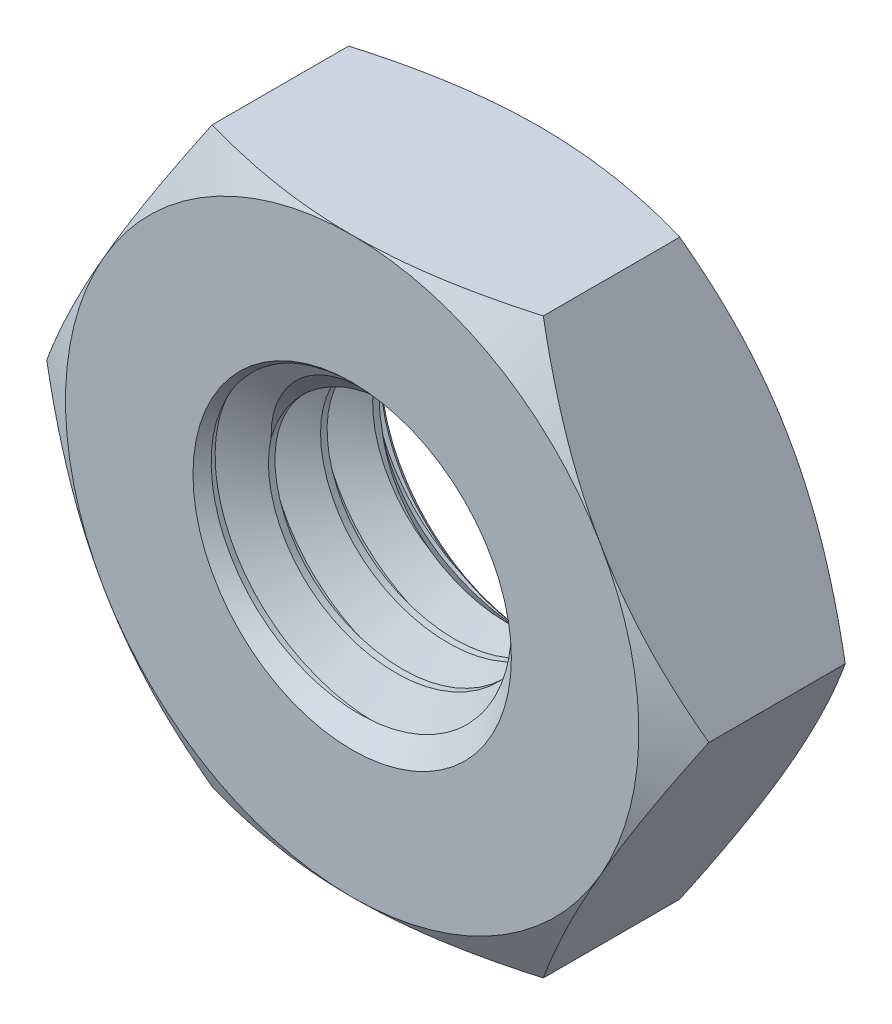
SolidWorks part; units mm, degrees
ref_plane "Front Plane" through (0, 0, 0) normal (0, 0, 1) x (1, 0, 0)
ref_plane "Top Plane" through (0, 0, 0) normal (0, 1, 0) x (1, 0, 0)
ref_plane "Right Plane" through (0, 0, 0) normal (1, 0, 0) x (0, 0, -1)
sketch "Sketch1" plane through (0, 0, 0) normal (1, 0, 0) x (0, 0, -1)
  line L0 (0, 2.75) -> (0, -2.75) construction
  line L1 (-0.9, 0) -> (0.9, 0) construction
  line L2 (-0.9, 1.5) -> (-0.9, -1.5) construction
  line L3 (-0.9, 1.5) -> (-0.4, 1.5) construction
  line L4 (-1.3687, 1.5541) -> (-0.8687, 1.5541) construction
  line L5 (-0.8687, 1.5541) -> (-0.9, 1.5) construction
  line L6 (-0.9, 1.5) -> (-1.1187, 1.1211) construction
  line L7 (-1.1187, 1.1211) -> (-1.3375, 1.5) construction
  line L8 (-1.3375, 1.5) -> (-1.3687, 1.5541) construction
  line L9 (-1.3375, 1.5) -> (-0.9, 1.5) construction
  line L10 (-1.15, 1.1752) -> (-1.0875, 1.1752) construction
  line L11 (-1.1187, 1.1752) -> (-1.1187, 1.1211) construction
  line L12 (-1.1187, 1.5541) -> (-1.1187, 1.5) construction
  point P4 (0, 0)
  point P8 (0, 0)
  point P11 (-0.9, 0)
  dimension "Thread OD" = 3
  dimension "Width" = 5.5
  dimension "Height" = 1.8
  dimension "D1" = 60
  dimension "D2" = 0.0625
  dimension "Thread Pitch" = 0.5
sketch "Sketch2" plane through (0, 0, 0) normal (0, 0, 1) x (1, 0, 0)
  line L1 (-1.5877, 2.75) -> (-3.1754, 0)
  line L2 (-3.1754, 0) -> (-1.5877, -2.75)
  line L3 (-1.5877, -2.75) -> (1.5877, -2.75)
  line L4 (1.5877, -2.75) -> (3.1754, 0)
  line L5 (3.1754, 0) -> (1.5877, 2.75)
  line L6 (1.5877, 2.75) -> (-1.5877, 2.75)
  circle A0 centre (0, 0) radius 2.75 construction
  circle A1 centre (0, 0) radius 1.5
extrude "Boss-Extrude1" add sketch "Sketch2" along normal up to vertex (0.9 mm away) and the other way up to vertex (0.9 mm away) up to point (0, 0, 0.9) other way up to point (0, 0, -0.9)
sketch "Sketch3" plane through (0, 0, 0.9) normal (0, 0, 1) x (1, 0, 0)
  circle A0 centre (0, 0) radius 2.75
extrude "Cut-Extrude1" cut sketch "Sketch3" against normal blind 10 draft 60 flip side to cut
sketch "Sketch4" plane through (0, 0, -0.9) normal (0, 0, -1) x (-1, 0, 0)
  circle A0 centre (0, 0) radius 2.75
extrude "Cut-Extrude2" cut sketch "Sketch4" against normal through all draft 60 flip side to cut
sketch "Sketch5" plane through (0, 0, 0) normal (1, 0, 0) x (0, 0, -1)
  line L10 (-1.3531, 1.5271) -> (-0.8844, 1.5271)
  line L12 (-1.3375, 1.5) -> (-1.3687, 1.5541) construction
  line L17 (-0.8687, 1.5541) -> (-0.9, 1.5) construction
  line L18 (-0.8844, 1.5271) -> (-1.0875, 1.1752)
  line L19 (-1.0875, 1.1752) -> (-1.15, 1.1752)
  line L20 (-1.15, 1.1752) -> (-1.3531, 1.5271)
sketch "Sketch8" plane through (0, 0, 0) normal (1, 0, 0) x (0, 0, -1)
  line L0 (-1.1187, 1.5541) -> (-1.1187, 1.5) construction
  line L1 (-0.9, 1.5) -> (-0.9, -1.5) construction
  line L2 (-1.3687, 1.9958) -> (0, 0.6271)
  line L3 (0, 2.75) -> (0, -2.75) construction
  line L4 (0, 0.6271) -> (1.3687, 1.9958)
  line L5 (1.3687, 1.9958) -> (1.3687, 0)
  line L6 (1.3687, 0) -> (-1.3687, 0)
  line L7 (-1.3687, 0) -> (-1.3687, 1.9958)
  point P0 (-1.1187, 1.5271)
  point P1 (-0.9, 1.5271)
  dimension "D1" = 45
revolve "Cut-Revolve2" cut sketch "Sketch8" angle 360 about L1
sketch "For Drawing" plane through (0, 0, 0.9) normal (0, 0, 1) x (1, 0, 0)
  line L0 (0, 0) -> (1.0607, -1.0607) construction
  point P3 (1.0607, -1.0607)
  dimension "D1" = 45
  dimension "D2" = 1.5
ref_axis "Center Axis 1" through (0, 0, 0.9) along (0, 0, -1)
sketch "Sketch6" plane through (0, 0, 0.9) normal (0, 0, 1) x (1, 0, 0)
  circle A0 centre (0, 0) radius 1.5
curve "Helix/Spiral1" pitch 0.5 height 2.3 radius 1.5 left hand yes centre (0, 0, 0.9) axis (0, 0, -1) start towards (0, 1, 0)
sweep "Sweep2" add profiles "Sketch5" path "Helix/Spiral1"
sketch "Sketch7" plane through (0, 0, 0) normal (1, 0, 0) x (0, 0, -1)
  line L0 (-1.65, 2.2771) -> (0, 0.6271)
  line L2 (-1.65, 2.2771) -> (-1.65, 0)
  line L8 (1.65, 0) -> (1.65, 2.2771)
  line L9 (0, 2.75) -> (0, -2.75) construction
  line L10 (0, 0.6271) -> (1.65, 2.2771)
  line L15 (-1.65, 0) -> (1.65, 0)
  line L18 (-1.1187, 1.5541) -> (-1.1187, 1.5) construction
  line L19 (-0.9, 1.5) -> (-0.9, -1.5) construction
  point P0 (-1.1187, 1.5271)
  point P6 (-0.9, 1.5271)
  dimension "D2" = 45
  dimension "D1" = 0.75
revolve "Cut-Revolve1" cut sketch "Sketch7" angle 360 about L1
equation "\"D4@Helix/Spiral1\" = \"Thread Pitch@Sketch1\""
equation "\"D3@Helix/Spiral1\" = \"Height@Sketch1\" + \"Thread Pitch@Sketch1\""
equation "\"D1@Sketch7\" = \"Thread Pitch@Sketch1\" * 1.5"
equation "\"D2@Sketch1\"= \"Thread Pitch@Sketch1\" / 8"
equation "\"D2@For Drawing\" = \"Thread OD@Sketch1\" / 2"
